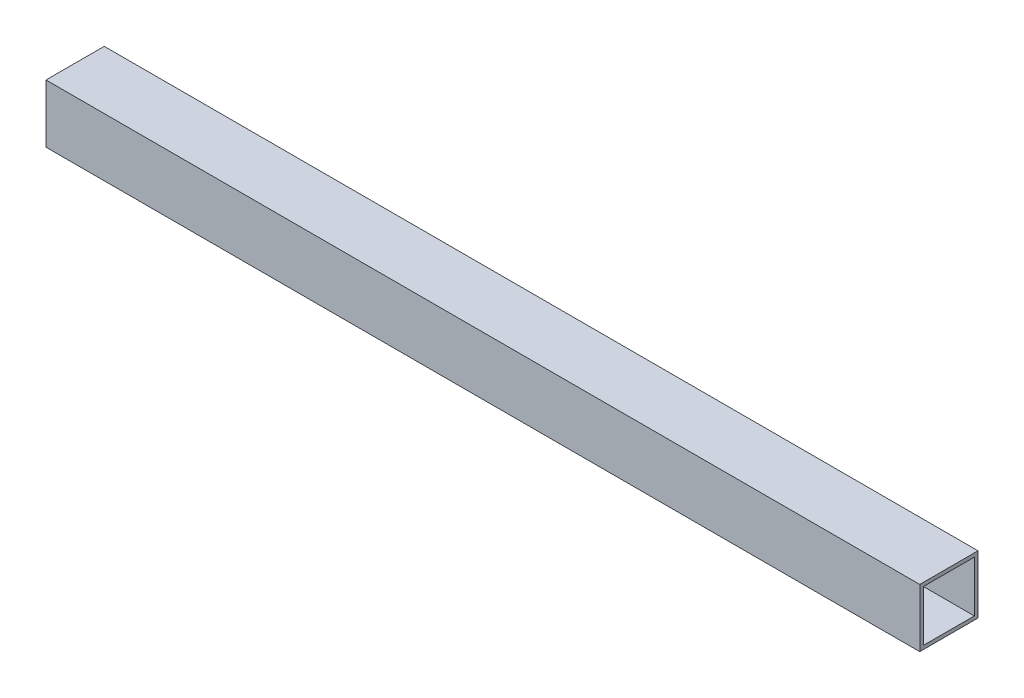
SolidWorks part; units mm, degrees
material "6061-T6 (SS)"
ref_plane "Front" through (0, 0, 0) normal (0, 0, 1) x (1, 0, 0)
ref_plane "Top" through (0, 0, 0) normal (0, 1, 0) x (1, 0, 0)
ref_plane "Right" through (0, 0, 0) normal (1, 0, 0) x (0, 0, -1)
sketch "Sketch1" plane through (0, 0, 0) normal (1, 0, 0) x (0, 0, -1)
  line L1 (12.7, -12.7) -> (-12.7, -12.7)
  line L2 (12.7, -12.7) -> (12.7, 12.7)
  line L3 (12.7, 12.7) -> (-12.7, 12.7)
  line L4 (-12.7, -12.7) -> (-12.7, 12.7)
  line L5 (12.7, -12.7) -> (-12.7, 12.7) construction
  line L6 (12.7, 12.7) -> (-12.7, -12.7) construction
  point P0 (0, 0)
  dimension "D1" = 25.4
extrude "Extrude-Thin1" add sketch "Sketch1" along normal up to surface (381 mm away) thin thin type one direction reverse wall 1.5875
